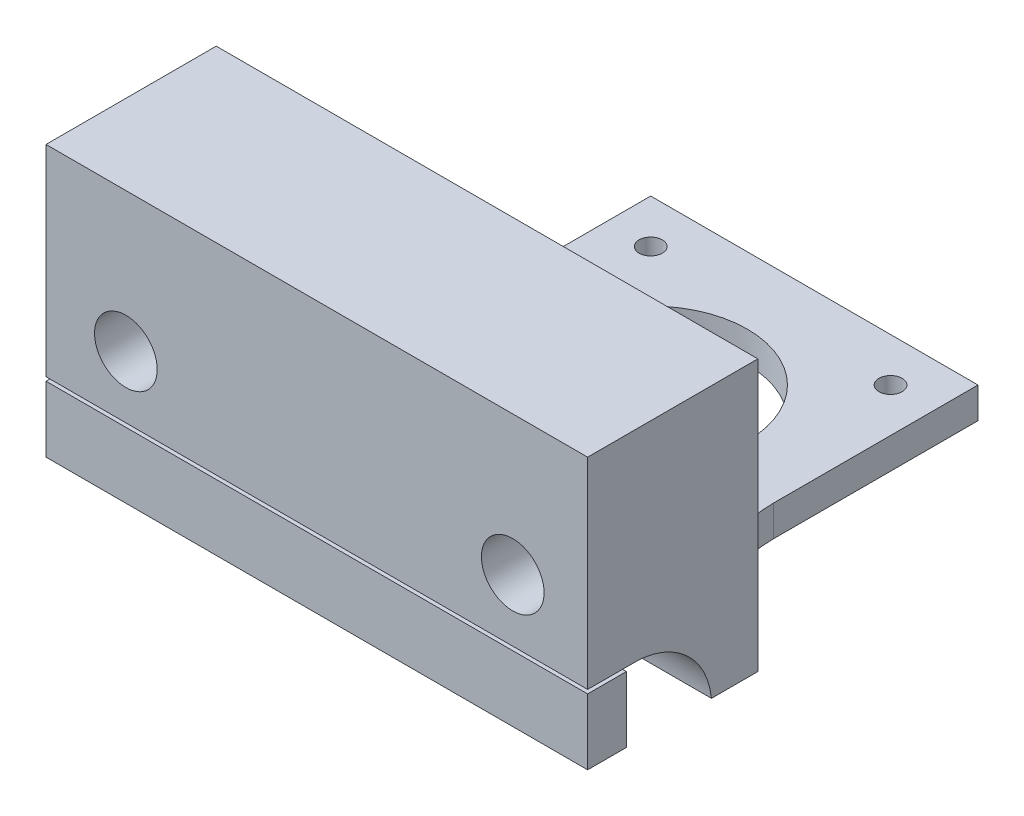
SolidWorks part; units mm, degrees
note: The reader was unsure of these and kept them because the rebuilt part matched: shared geometry of "Sketch5<2>".
ref_plane "Front Plane" through (0, 0, 0) normal (0, 0, 1) x (1, 0, 0)
ref_plane "Top Plane" through (0, 0, 0) normal (0, 1, 0) x (1, 0, 0)
ref_plane "Right Plane" through (0, 0, 0) normal (1, 0, 0) x (0, 0, -1)
sketch "Sketch1" plane through (0, 0, 0) normal (0, 1, 0) x (1, 0, 0)
  line L1 (-15.5, 15.5) -> (15.5, 15.5)
  line L2 (-15.5, 15.5) -> (-15.5, -15.5)
  line L3 (-15.5, -15.5) -> (15.5, -15.5)
  line L4 (15.5, 15.5) -> (15.5, -15.5)
  line L5 (-15.5, 15.5) -> (15.5, -15.5) construction
  line L6 (-15.5, -15.5) -> (15.5, 15.5) construction
  line L7 (-21.15, 21.15) -> (21.15, 21.15)
  line L8 (-21.15, 21.15) -> (-21.15, -21.15)
  line L9 (-21.15, -21.15) -> (21.15, -21.15)
  line L10 (21.15, 21.15) -> (21.15, -21.15)
  line L11 (-21.15, 21.15) -> (21.15, -21.15) construction
  line L12 (-21.15, -21.15) -> (21.15, 21.15) construction
  circle A0 centre (-15.5, 15.5) radius 1.5
  circle A1 centre (15.5, 15.5) radius 1.5
  circle A2 centre (15.5, -15.5) radius 1.5
  circle A3 centre (-15.5, -15.5) radius 1.5
  circle A4 centre (0, 0) radius 12.5
  point P0 (0, 0)
  point P6 (0, 0)
  dimension "D5" = 3
  dimension "D6" = 25
  dimension "D1" = 42.3
  dimension "D2" = 42.3
  dimension "D3" = 31
  dimension "D4" = 31
extrude "Boss-Extrude1" add sketch "Sketch1" along normal blind 4 contours A4 | L1 A0 L2 | L2 A0 L1 | L3 A2 L4 | L4 A2 L3 | L2 A3 L3 | L3 A3 L2 | L7 L10 L9 L8 | A1
sketch "Sketch2" plane through (0, 0, 21.15) normal (0, 0, 1) x (1, 0, 0)
  line L1 (-35, 0) -> (35, 0)
  line L2 (-35, 0) -> (-35, 35)
  line L3 (-35, 35) -> (35, 35)
  line L4 (35, 0) -> (35, 35)
  line L6 (-35, 35) -> (35, 35)
  line L7 (-35, 35) -> (-35, 16)
  line L8 (-35, 16) -> (35, 16)
  line L9 (35, 35) -> (35, 16)
  dimension "D3" = 35
  dimension "D1" = 70
  dimension "D2" = 35
  dimension "D7" = 19
extrude "Boss-Extrude3" add sketch "Sketch2" along normal blind 6
sketch "Sketch5" plane through (0, 0, 27.15) normal (0, 0, 1) x (1, 0, 0)
  line L0 (35, 0) -> (35, 35) construction
  line L1 (-35, 35) -> (35, 35)
  line L2 (-35, 35) -> (-35, 9)
  line L3 (-35, 9) -> (35, 9)
  line L4 (35, 35) -> (35, 9)
  line L5 (-35, 0) -> (35, 0) construction
  circle A0 centre (-24.679, 17) radius 4.05
  circle A1 centre (25.321, 17) radius 4.05
  dimension "D2" = 8.1
  dimension "D1" = 26
  dimension "D3" = 18
  dimension "D4" = 50
extrude "Boss-Extrude7" add sketch "Sketch5" along normal blind 16
extrude "Cut-Extrude1" cut sketch "Sketch5<2>" against normal blind 16 contours A0 | A1
sketch "Sketch5<2>" plane through (0, 0, 27.15) normal (0, 0, 1) x (1, 0, 0) same geometry as "Sketch5"
fillet "Fillet1" radius 16 2 edges
fillet "Fillet2" radius 10 1 edges
fillet "Fillet4" radius 2 1 edges at (0, 4, 21.15)
sketch "Sketch6" plane through (0, 0, 0) normal (0, -1, 0) x (1, 0, 0)
  line L1 (-35, 43.15) -> (35, 43.15)
  line L2 (-35, 43.15) -> (-35, 38.15)
  line L3 (-35, 38.15) -> (35, 38.15)
  line L4 (35, 43.15) -> (35, 38.15)
  dimension "D1" = 5
extrude "Boss-Extrude8" add sketch "Sketch6" against normal offset from surface (8.5 mm away) 0.5 separate body up to face at (0, 9, 41.6375)
